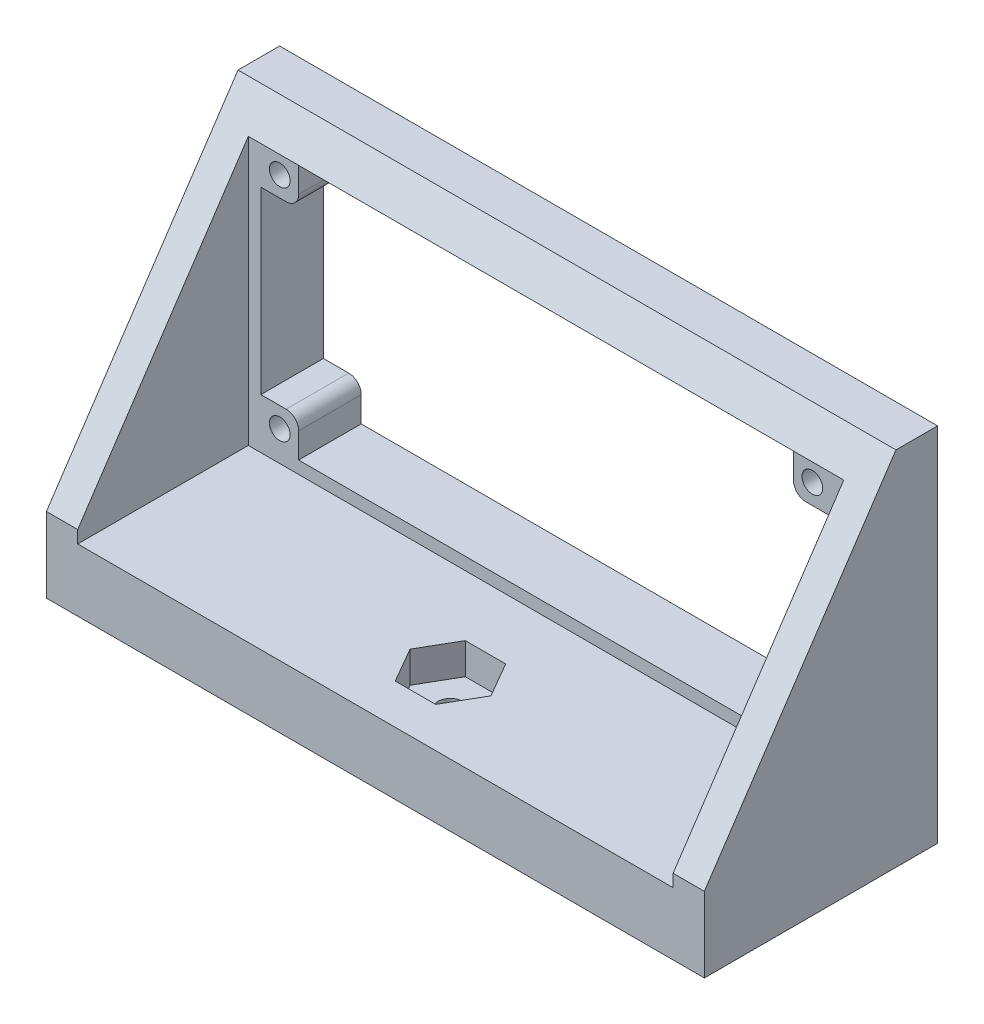
SolidWorks part; units mm, degrees
ref_plane "Plan de face" through (0, 0, 0) normal (0, 0, 1) x (1, 0, 0)
ref_plane "Plan de dessus" through (0, 0, 0) normal (0, 1, 0) x (1, 0, 0)
ref_plane "Plan de droite" through (0, 0, 0) normal (1, 0, 0) x (0, 0, -1)
sketch "Esquisse1" plane through (0, 0, 0) normal (0, 0, 1) x (1, 0, 0)
  line L1 (-21.285, -8.79) -> (21.285, -8.79) construction
  line L2 (-21.285, -8.79) -> (-21.285, 8.79) construction
  line L3 (-21.285, 8.79) -> (21.285, 8.79) construction
  line L4 (21.285, -8.79) -> (21.285, 8.79) construction
  line L5 (-21.285, -8.79) -> (21.285, 8.79) construction
  line L6 (-21.285, 8.79) -> (21.285, -8.79) construction
  line L7 (-22.795, -10.2) -> (22.795, -10.2)
  line L8 (-22.795, -10.2) -> (-22.795, 10.2)
  line L9 (-22.795, 10.2) -> (22.795, 10.2)
  line L10 (22.795, -10.2) -> (22.795, 10.2)
  line L11 (-22.795, -10.2) -> (22.795, 10.2) construction
  line L12 (-22.795, 10.2) -> (22.795, -10.2) construction
  circle A0 centre (-21.285, 8.79) radius 0.825
  circle A1 centre (21.285, 8.79) radius 0.825
  circle A2 centre (21.285, -8.79) radius 0.825
  circle A3 centre (-21.285, -8.79) radius 0.825
  point P0 (0, 0)
  point P6 (0, 0)
  dimension "D5" = 1.65
  dimension "D1" = 42.57
  dimension "D2" = 17.58
  dimension "D3" = 20.4
  dimension "D4" = 45.59
extrude "Boss.-Extru.1" add sketch "Esquisse1" along normal blind 5
sketch "Esquisse2" plane through (0, -10.2, 0) normal (0, -1, 0) x (1, 0, 0)
  line L0 (-22.795, 5) -> (22.795, 5) construction
  line L1 (-22.795, 0) -> (22.795, 0)
  line L2 (-22.795, 0) -> (-22.795, 18.64)
  line L3 (-22.795, 18.64) -> (22.795, 18.64)
  line L4 (22.795, 0) -> (22.795, 18.64)
  dimension "D1" = 13.64
extrude "Boss.-Extru.2" add sketch "Esquisse2" along normal blind 6
sketch "Esquisse3" plane through (0, -10.2, 0) normal (0, 1, 0) x (1, 0, 0)
  line L0 (22.795, -5) -> (22.795, -18.64) construction
  line L1 (-22.795, -18.64) -> (22.795, -18.64) construction
  line L2 (-22.795, -18.64) -> (-22.795, -6.64) construction
  line L3 (-22.795, -6.64) -> (22.795, -6.64) construction
  line L4 (22.795, -18.64) -> (22.795, -6.64) construction
  line L5 (-22.795, -6.64) -> (22.795, -18.64) construction
  circle A0 centre (0, -12.64) radius 1
  dimension "D2" = 2
  dimension "D1" = 12
extrude "Enlèv. mat.-Extru.1" cut sketch "Esquisse3" against normal blind 6
sketch "Esquisse4" plane through (0, -10.2, 0) normal (0, 1, 0) x (1, 0, 0)
  line L0 (22.795, -18.64) -> (-22.795, -18.64) construction
  line L1 (1.6166, -15.44) -> (3.2332, -12.64)
  line L2 (3.2332, -12.64) -> (1.6166, -9.84)
  line L3 (1.6166, -9.84) -> (-1.6166, -9.84)
  line L4 (-1.6166, -9.84) -> (-3.2332, -12.64)
  line L5 (-3.2332, -12.64) -> (-1.6166, -15.44)
  line L6 (-1.6166, -15.44) -> (1.6166, -15.44)
  circle A0 centre (0, -12.64) radius 2.8 construction
  dimension "D1" = 5.6
extrude "Enlèv. mat.-Extru.2" cut sketch "Esquisse4" against normal blind 3.5
sketch "Esquisse5" plane through (0, 0, 0) normal (0, 0, -1) x (-1, 0, 0)
  line L0 (-22.795, 10.2) -> (22.795, 10.2) construction
  line L1 (-19.775, 10.2) -> (19.775, 10.2)
  line L2 (-19.775, 10.2) -> (-19.775, -10.2)
  line L3 (-19.775, -10.2) -> (19.775, -10.2)
  line L4 (19.775, 10.2) -> (19.775, -10.2)
  line L6 (-22.795, 10.2) -> (-19.775, 10.2) construction
  line L9 (1.6166, -10.2) -> (-1.6166, -10.2) construction
  point P6 (-19.775, -10.3866)
  point P8 (0, 10.2)
  point P11 (-21.285, 8.79)
  point P13 (-21.285, 10.2)
  point P14 (0, 0)
  point P15 (0, 0)
  point P17 (-19.775, -11.1046)
extrude "Enlèv. mat.-Extru.3" cut sketch "Esquisse5" against normal blind 5
sketch "Esquisse6" plane through (-22.795, 0, 0) normal (-1, 0, 0) x (0, 0, 1)
  line L0 (0, 10.2) -> (5, 10.2)
  line L1 (5, 10.2) -> (18.64, -10.2)
  line L2 (18.64, -10.2) -> (18.64, -16.2)
  line L3 (18.64, -16.2) -> (0, -16.2)
  line L4 (0, -16.2) -> (0, 10.2)
extrude "Boss.-Extru.3" add sketch "Esquisse6" along normal blind 3.5
sketch "Esquisse7" plane through (22.795, 0, 0) normal (1, 0, 0) x (0, 0, -1)
  line L0 (0, 10.2) -> (-5, 10.2)
  line L1 (-5, 10.2) -> (-18.64, -10.2)
  line L2 (-18.64, -10.2) -> (-18.64, -16.2)
  line L3 (-18.64, -16.2) -> (0, -16.2)
  line L4 (0, -16.2) -> (0, 10.2)
extrude "Boss.-Extru.4" add sketch "Esquisse7" along normal blind 3.5
sketch "Esquisse8" plane through (0, 0, 0) normal (0, 0, -1) x (-1, 0, 0)
  line L0 (-22.795, -10.2) -> (-22.795, 10.2) construction
  line L1 (-22.795, 7.18) -> (22.795, 7.18)
  line L2 (-22.795, 7.18) -> (-22.795, -7.18)
  line L3 (-22.795, -7.18) -> (22.795, -7.18)
  line L4 (22.795, 7.18) -> (22.795, -7.18)
  line L5 (22.795, -10.2) -> (22.795, 10.2) construction
  line L6 (-20.7479, 7.18) -> (-20.7479, 10.2) construction
  line L7 (-26.295, 10.2) -> (-19.775, 10.2) construction
  line L8 (-22.795, 6.897) -> (-19.775, 6.897) construction
  line L9 (-19.775, 10.2) -> (-19.775, -10.2) construction
  line L10 (-18.5049, -10.2) -> (-18.5049, -7.18) construction
  line L11 (-19.775, -10.2) -> (19.775, -10.2) construction
extrude "Enlèv. mat.-Extru.4" cut sketch "Esquisse8" against normal blind 5
sketch "Esquisse10" plane through (22.795, 0, 0) normal (-1, 0, 0) x (0, 0, 1)
  line L0 (5, 10.2) -> (18.64, -10.2)
  line L1 (18.64, -10.2) -> (5, -10.2)
  line L2 (5, -10.2) -> (5, 10.2)
extrude "Enlèv. mat.-Extru.5" cut sketch "Esquisse10" against normal blind 1
sketch "Esquisse11" plane through (-22.795, 0, 0) normal (1, 0, 0) x (0, 0, -1)
  line L0 (-5, 10.2) -> (-18.64, -10.2)
  line L1 (-18.64, -10.2) -> (-5, -10.2)
  line L2 (-5, -10.2) -> (-5, 10.2)
extrude "Enlèv. mat.-Extru.6" cut sketch "Esquisse11" against normal blind 1
sketch "Esquisse12" plane through (0, -10.2, 0) normal (0, 1, 0) x (1, 0, 0)
  line L1 (-23.795, -5) -> (23.795, -5)
  line L2 (-23.795, -5) -> (-23.795, -18.64)
  line L3 (-23.795, -18.64) -> (23.795, -18.64)
  line L4 (23.795, -5) -> (23.795, -18.64)
extrude "Enlèv. mat.-Extru.7" cut sketch "Esquisse12" against normal blind 1
fillet "Congé2" radius 1 4 edges at (19.775, 7.18, 2.5) (19.775, -7.18, 2.5) (-19.775, -7.18, 2.5) (-19.775, 7.18, 2.5)
sketch "Esquisse13" plane through (0, 10.2, 0) normal (0, 1, 0) x (1, 0, 0)
  line L1 (-26.295, -5) -> (26.295, -5)
  line L2 (-26.295, -5) -> (-26.295, 0)
  line L3 (-26.295, 0) -> (26.295, 0)
  line L4 (26.295, -5) -> (26.295, 0)
extrude "Boss.-Extru.5" add sketch "Esquisse13" along normal blind 2.5
sketch "Esquisse14" plane through (-26.295, 0, 0) normal (-1, 0, 0) x (0, 0, 1)
  line L0 (5, 10.2) -> (2.5, 13.939)
  line L1 (2.5, 13.939) -> (5, 13.939)
  line L2 (5, 12.7) -> (5, 10.2) construction
  line L3 (5, 13.939) -> (5, 10.2)
  line L4 (18.64, -10.2) -> (5, 10.2) construction
  dimension "D1" = 2.5
extrude "Enlèv. mat.-Extru.8" cut sketch "Esquisse14" against normal blind 53.5
sketch "Esquisse15" plane through (0, -16.2, 0) normal (0, -1, 0) x (-1, 0, 0)
  circle A0 centre (0, -12.64) radius 29.1753 construction
